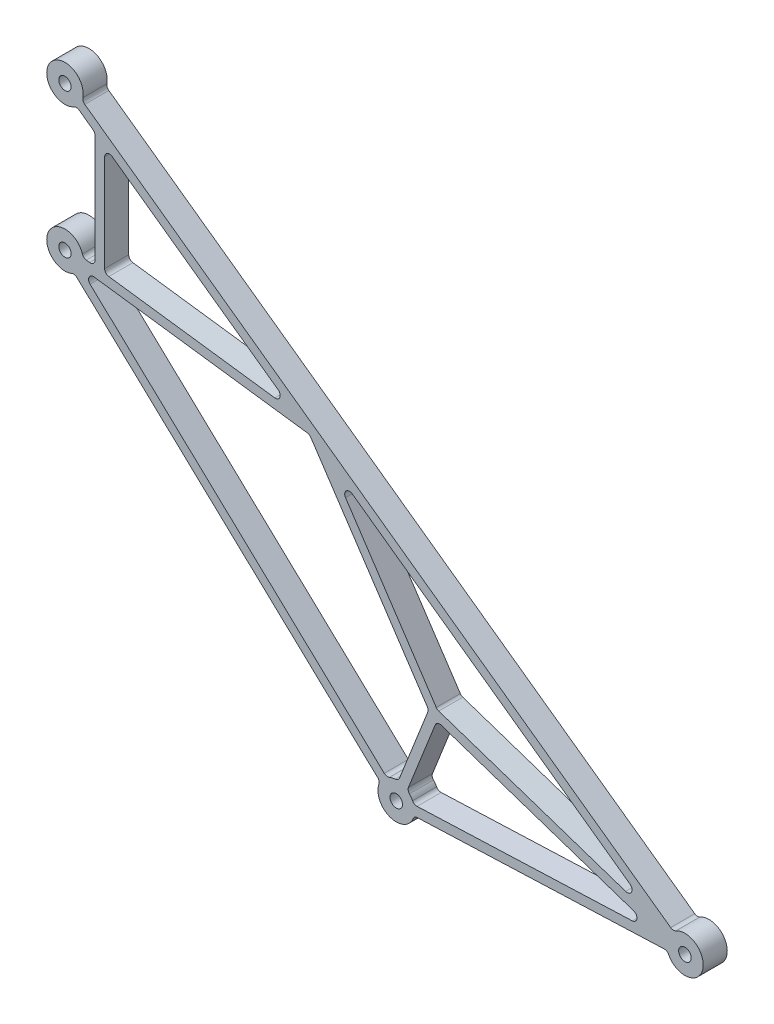
SolidWorks part; units mm, degrees
material "6061-T6 (SS)"
ref_plane "Front Plane" through (0, 0, 0) normal (0, 0, 1) x (1, 0, 0)
ref_plane "Top Plane" through (0, 0, 0) normal (0, 1, 0) x (1, 0, 0)
ref_plane "Right Plane" through (0, 0, 0) normal (1, 0, 0) x (0, 0, -1)
sketch "Sketch1" plane through (0, 0, 0) normal (0, 0, 1) x (1, 0, 0)
  line L4 (317.7817, -31.328) -> (165.3837, -37.3201) construction
  line L5 (317.7817, -31.328) -> (-9.5162, 203.2433) construction
  line L6 (-9.5162, 203.2433) -> (-9.5162, 127.0433) construction
  line L7 (-9.5162, 127.0433) -> (165.3837, -37.3201) construction
  line L8 (-3.9165, 211.0581) -> (323.4036, -23.4823)
  line L9 (165.3837, -46.9721) -> (317.7817, -40.98)
  line L10 (158.7728, -44.3526) -> (-16.101, 120.0386)
  line L11 (6.3588, 180.0409) -> (6.3588, 136.6572)
  line L12 (0.0088, 25.4433) -> (0.0088, 254.0433) construction
  line L13 (-15.1158, 195.4285) -> (6.3588, 180.0409)
  line L14 (6.3588, 136.6572) -> (-9.5162, 136.6572)
  circle A0 centre (317.7817, -31.328) radius 3.302 construction
  circle A1 centre (165.3837, -37.3201) radius 3.302 construction
  circle A2 centre (-9.5162, 203.2433) radius 3.2639 construction
  circle A3 centre (-9.5162, 127.0433) radius 3.2639 construction
  circle A5 centre (165.3837, -37.3201) radius 3.302
  circle A8 centre (317.7817, -31.328) radius 3.302
  circle A9 centre (317.7817, -31.328) radius 9.652
  circle A10 centre (165.3837, -37.3201) radius 9.652
  circle A15 centre (-9.5162, 127.0433) radius 3.2639
  circle A16 centre (-9.5162, 203.2433) radius 3.2639
  circle A17 centre (-9.5162, 203.2433) radius 9.6139
  circle A18 centre (-9.5162, 127.0433) radius 9.6139
  dimension "D4" = 43.3837
  dimension "D3" = 6.35
  dimension "D1" = 6.35
  dimension "D2" = 6.35
extrude "Boss-Extrude1" add sketch "Sketch1" along normal mid plane 12.7 contours A10 L9 A9 | A9 A8 | A10 L9 A5 | A18 A15 | A17 A16 region at (137.1527, 54.5081, 0) region at (-1.2064, 207.5118, 0) region at (326.1244, -27.0426, 0) region at (165.7519, -46.6844, 0) region at (-2.9104, 133.6491, 0)
fillet "Fillet1" radius 6.35 2 edges at (6.3588, 180.0409, 0) (6.3588, 136.6572, 0)
sketch "Sketch3" plane through (0, 0, 0) normal (0, 0, 1) x (1, 0, 0)
  line L0 (-9.5162, 203.2433) -> (317.7817, -31.328) construction
  line L1 (317.7817, -31.328) -> (165.3837, -37.3201) construction
  line L2 (165.3837, -37.3201) -> (-9.5162, 127.0433) construction
  line L3 (165.3837, -37.3201) -> (185.3536, 13.0931) construction
  line L4 (-9.5162, 127.0433) -> (121.0882, 109.6404) construction
  line L5 (317.7817, -31.328) -> (185.3536, 13.0931) construction
  line L6 (6.3588, 176.7791) -> (6.3588, 143.0072)
  line L7 (0.0088, 136.6572) -> (-9.5162, 136.6572)
  line L8 (-16.101, 120.0386) -> (158.7728, -44.3526)
  line L9 (165.3837, -46.9721) -> (317.7817, -40.98)
  line L10 (323.4036, -23.4823) -> (-3.9165, 211.0581)
  line L11 (-15.1158, 195.4285) -> (3.7074, 181.9408)
  line L12 (6.3588, 176.7791) -> (6.3588, 143.0072)
  line L13 (0.0088, 136.6572) -> (-9.5162, 136.6572)
  line L14 (-16.101, 120.0386) -> (158.7728, -44.3526)
  line L15 (165.3837, -46.9721) -> (317.7817, -40.98)
  line L16 (323.4036, -23.4823) -> (-3.9165, 211.0581)
  line L17 (-15.1158, 195.4285) -> (3.7074, 181.9408)
  line L18 (121.0882, 109.6404) -> (185.3536, 13.0931) construction
  line L19 (-10.9958, 201.1788) -> (316.3021, -33.3926)
  line L20 (167.1231, -35.4691) -> (-2.0171, 123.4816)
  line L21 (-2.0171, 123.4816) -> (119.6116, 107.2747)
  line L22 (119.6116, 107.2747) -> (183.2392, 11.6857)
  line L23 (318.5895, -28.9199) -> (186.1614, 15.5012)
  line L24 (167.7452, -38.2555) -> (187.7151, 12.1576)
  line L25 (317.6819, -28.79) -> (165.2839, -34.782)
  line L26 (-8.0365, 205.3079) -> (319.2613, -29.2635)
  line L27 (163.6443, -39.171) -> (-17.0152, 130.605)
  line L28 (-17.0152, 130.605) -> (122.0523, 112.0744)
  line L29 (122.9452, 111.4344) -> (187.468, 14.5005)
  line L30 (316.9739, -33.7362) -> (184.5459, 10.6849)
  line L31 (163.0222, -36.3846) -> (182.9922, 14.0285)
  line L32 (317.8815, -33.8661) -> (165.4835, -39.8581)
  line L33 (-17.0152, 130.605) -> (122.5647, 112.0061) construction
  line L34 (122.5647, 112.0061) -> (187.468, 14.5005) construction
  line L35 (11.4388, 185.1001) -> (11.4388, 126.8135)
  line L36 (6.3588, 188.7409) -> (6.3588, 127.4905)
  circle A0 centre (317.7817, -31.328) radius 3.302 construction
  circle A1 centre (165.3837, -37.3201) radius 3.302 construction
  circle A2 centre (-9.5162, 127.0433) radius 3.2639 construction
  circle A3 centre (-9.5162, 203.2433) radius 3.2639 construction
  circle A4 centre (317.7817, -31.328) radius 3.302
  circle A5 centre (165.3837, -37.3201) radius 3.302
  arc A6 (0.0088, 136.6572) -> (6.3588, 143.0072) centre (0.0088, 143.0072) ccw
  arc A7 (-9.5162, 136.6572) -> (-16.101, 120.0386) centre (-9.5162, 127.0433) ccw
  arc A8 (158.7728, -44.3526) -> (165.3837, -46.9721) centre (165.3837, -37.3201) ccw
  arc A9 (317.7817, -40.98) -> (323.4036, -23.4823) centre (317.7817, -31.328) ccw
  arc A10 (-3.9165, 211.0581) -> (-15.1158, 195.4285) centre (-9.5162, 203.2433) ccw
  arc A11 (6.3588, 176.7791) -> (3.7074, 181.9408) centre (0.0088, 176.7791) ccw
  arc A12 (0.0088, 136.6572) -> (6.3588, 143.0072) centre (0.0088, 143.0072) ccw
  arc A13 (-9.5162, 136.6572) -> (-16.101, 120.0386) centre (-9.5162, 127.0433) ccw
  arc A14 (158.7728, -44.3526) -> (165.3837, -46.9721) centre (165.3837, -37.3201) ccw
  arc A15 (317.7817, -40.98) -> (323.4036, -23.4823) centre (317.7817, -31.328) ccw
  arc A16 (-3.9165, 211.0581) -> (-15.1158, 195.4285) centre (-9.5162, 203.2433) ccw
  arc A17 (6.3588, 176.7791) -> (3.7074, 181.9408) centre (0.0088, 176.7791) ccw
  circle A18 centre (-9.5162, 127.0433) radius 3.2639
  circle A19 centre (-9.5162, 203.2433) radius 3.2639
  circle A20 centre (-9.5162, 203.2433) radius 9.6139
  circle A21 centre (-9.5162, 127.0433) radius 9.6139
  circle A22 centre (317.7817, -31.328) radius 9.652
  circle A23 centre (165.3837, -37.3201) radius 9.652
  dimension "D5" = 5.08
  dimension "D1" = 0
  dimension "D2" = 6.35
  dimension "D3" = 2.54
  dimension "D4" = 2.54
extrude "Cut-Extrude1" cut sketch "Sketch3" against normal through all both and the other way through all contours A20 L17 A17 L36 L19 | A22 L16 A20 L26 | L19 L35 L28 | A23 L31 L22 L21 A21 L20 | A23 L27 A21 L14 | L19 L29 L23 | A23 L25 L30 L24 | A23 L15 A22 L32 | A21 L28 L36 A12 L13 region at (-0.7734, 188.9342, 0) region at (2.1827, 133.4152, 0) region at (44.7393, 141.8051, 0) region at (157.8146, 90.8329, 0) region at (73.7991, 40.3454, 0) region at (206.8149, 30.3884, 0) region at (107.4003, 57.995, 0) region at (241.8244, -40.4704, 0) region at (220.2027, -17.938, 0)
fillet "Fillet2" radius 2.54 25 edges at (302.5581, -23.5424, 0) (303.8498, -29.3339, 0) (311.6926, -23.8391, 0) (308.5769, -34.2319, 0) (174.7881, -39.4923, 0) (156.8586, -32.7941, 0) (160.3375, -29.0923, 0) (166.4516, -27.7273, 0) (171.1746, -29.5982, 0) (174.5885, -34.4162, 0) (186.9861, 15.2246, 0) (182.5025, 12.7924, 0) (186.8284, 9.9193, 0) (-4.4987, 118.8426, 0) (0.0104, 128.3364, 0) (-0.6606, 123.3009, 0) (130.9006, 99.483, 0) (119.6116, 107.2747, 0) (111.3401, 113.5018, 0) (-3.4592, 195.7774, 0) (-0.4999, 199.9065, 0) (6.3588, 188.7409, 0) (11.4388, 185.1001, 0) (11.4388, 126.8135, 0) (6.3588, 127.4905, 0)
fillet "Fillet3" radius 2.54 1 edges at (-1.0199, 122.5445, 0)
